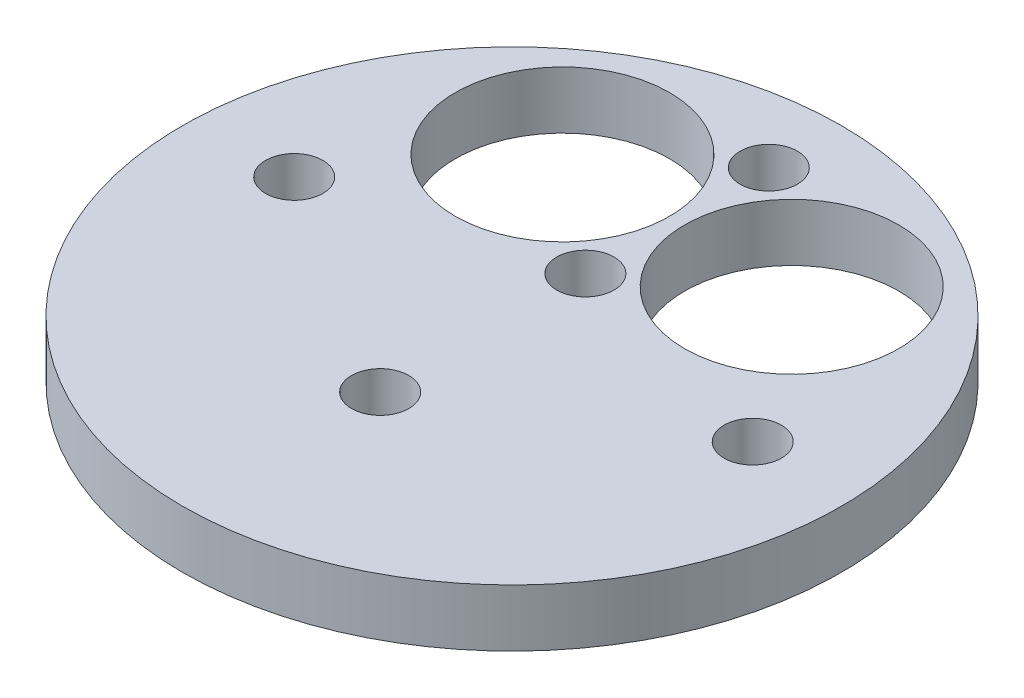
SolidWorks part; units mm, degrees
material "G10 Fiberglass"
ref_plane "Front Plane" through (0, 0, 0) normal (0, 0, 1) x (1, 0, 0)
ref_plane "Top Plane" through (0, 0, 0) normal (0, 1, 0) x (1, 0, 0)
ref_plane "Right Plane" through (0, 0, 0) normal (1, 0, 0) x (0, 0, -1)
ref_axis "Axis1" through (0, 55, 0) along (0, -1, 0)
sketch "Sketch1" plane through (0, 0, 0) normal (0, 0, 1) x (1, 0, 0)
  line L0 (0, 0) -> (36.5125, 0)
  line L3 (36.5125, 0) -> (36.5125, 6.35)
  line L4 (36.5125, 6.35) -> (0, 6.35)
  line L5 (0, 55) -> (0, -55) construction
  line L6 (0, 6.35) -> (0, 0)
  line L7 (0, 0) -> (0, 21.2966) construction
  dimension "D1" = 73.025
  dimension "D2" = 6.35
revolve "Revolve1" add sketch "Sketch1" angle 360 about L7
sketch "Sketch2" plane through (0, 6.35, 0) normal (0, 1, 0) x (1, 0, 0)
  line L0 (-12.7, 18.288) -> (12.7, 18.288) construction
  line L1 (0, 28.448) -> (0, 8.128) construction
  line L2 (-12.7, 18.288) -> (12.7, 18.288) construction
  line L3 (-12.7, 32.258) -> (12.7, 32.258) construction
  line L4 (-12.7, 4.318) -> (12.7, 4.318) construction
  circle A0 centre (-12.7, 18.288) radius 11.8745
  circle A1 centre (0, 0) radius 36.5125
  circle A3 centre (12.7, 18.288) radius 11.8745
  circle A4 centre (0, 28.448) radius 3.175
  circle A5 centre (0, 8.128) radius 3.175
  arc A6 (-12.7, 32.258) -> (-12.7, 4.318) centre (-12.7, 18.288) ccw construction
  arc A7 (12.7, 4.318) -> (12.7, 32.258) centre (12.7, 18.288) ccw construction
  circle A8 centre (0, -14.605) radius 3.175
  circle A9 centre (0, 0) radius 34.163 construction
  circle A11 centre (0, 0) radius 36.5125 construction
  point P11 (0, 18.288)
  point P12 (0, 18.288)
  point P15 (0, 18.288)
  dimension "D2" = 23.749
  dimension "D3" = 23.749
  dimension "D5" = 6.35
  dimension "D6" = 6.35
  dimension "D11" = 6.35
  dimension "D4" = 25.4
  dimension "D7" = 20.32
  dimension "D8" = 25.4
  dimension "D9" = 27.94
  dimension "D10" = 14.605
  dimension "D12" = 4.318
  dimension "D1" = 0
extrude "Cut-Extrude1" cut sketch "Sketch2" against normal through all both and the other way through all
sketch "Sketch3" plane through (0, 6.35, 0) normal (0, 1, 0) x (1, 0, 0)
  line L0 (-25.4, 1.27) -> (25.4, 1.27) construction
  circle A0 centre (-25.4, 1.27) radius 3.175
  circle A1 centre (25.4, 1.27) radius 3.175
  point P4 (0, 1.27)
  dimension "D1" = 6.35
  dimension "D2" = 6.35
  dimension "D3" = 50.8
  dimension "D4" = 1.27
extrude "Cut-Extrude2" cut sketch "Sketch3" against normal through all both
ref_plane "Plane1" through (0, 3.175, 0) normal (0, 1, 0) x (-1, 0, 0)
equation "\"D3@Sketch2\"=\"D2@Sketch2\""
equation "\"D6@Sketch2\"=\"D5@Sketch2\""
